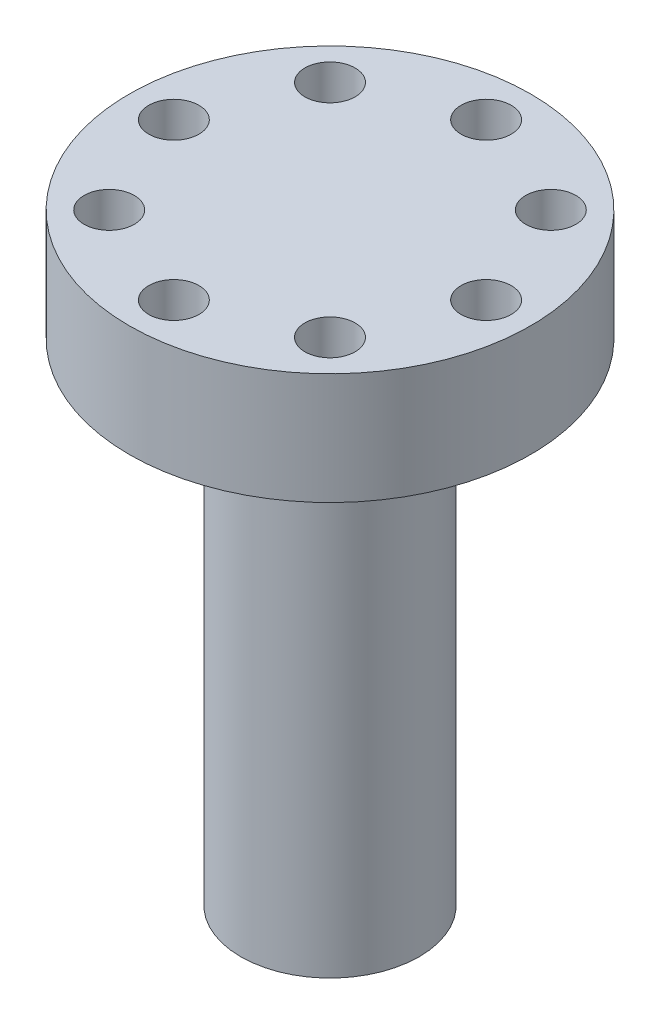
SolidWorks part; units mm, degrees
ref_plane "Front Plane" through (0, 0, 0) normal (0, 0, 1) x (1, 0, 0)
ref_plane "Top Plane" through (0, 0, 0) normal (0, 1, 0) x (1, 0, 0)
ref_plane "Right Plane" through (0, 0, 0) normal (1, 0, 0) x (0, 0, -1)
sketch "Sketch1" plane through (0, 0, 0) normal (0, 1, 0) x (1, 0, 0)
  circle A0 centre (0, 0) radius 9
  dimension "D1" = 18
extrude "BracketMount" add sketch "Sketch1" along normal blind 5
sketch "Sketch2" plane through (0, 5, 0) normal (0, 1, 0) x (1, 0, 0)
  circle A0 centre (0, 7) radius 1.125
  circle A7 centre (4.9497, 4.9497) radius 1.125
  circle A8 centre (7, 0) radius 1.125
  circle A9 centre (4.9497, -4.9497) radius 1.125
  circle A10 centre (0, -7) radius 1.125
  circle A11 centre (-4.9497, -4.9497) radius 1.125
  circle A12 centre (-7, 0) radius 1.125
  circle A13 centre (-4.9497, 4.9497) radius 1.125
  point P19 (0, 0)
  dimension "D1" = 2.25
  dimension "D3" = 7
extrude "Bracket-MountHoles" cut sketch "Sketch2" against normal up to surface (5 mm away) up to face at (0, 0, 9)
sketch "Sketch3" plane through (0, 0, 0) normal (0, -1, 0) x (1, 0, 0)
  circle A0 centre (0, 0) radius 4
  dimension "D1" = 8
extrude "StepperSleeve" add sketch "Sketch3" along normal blind 22
sketch "Sketch4" plane through (0, -22, 0) normal (0, -1, 0) x (1, 0, 0)
  circle A0 centre (0, 0) radius 2.51
  dimension "D1" = 5.02
extrude "InitialSeat" cut sketch "Sketch4" against normal blind 9
sketch "Sketch5" plane through (0, -13, 0) normal (0, -1, 0) x (1, 0, 0)
  line L3 (1.89, 1.6517) -> (1.89, -1.6517)
  arc A6 (1.89, 1.6517) -> (1.89, -1.6517) centre (0, 0) ccw
  point P7 (-2.51, 0)
  dimension "D1" = 4.4
extrude "OrientationNub" cut sketch "Sketch5" against normal up to surface (13 mm away) up to face at (0, 0, 4)
